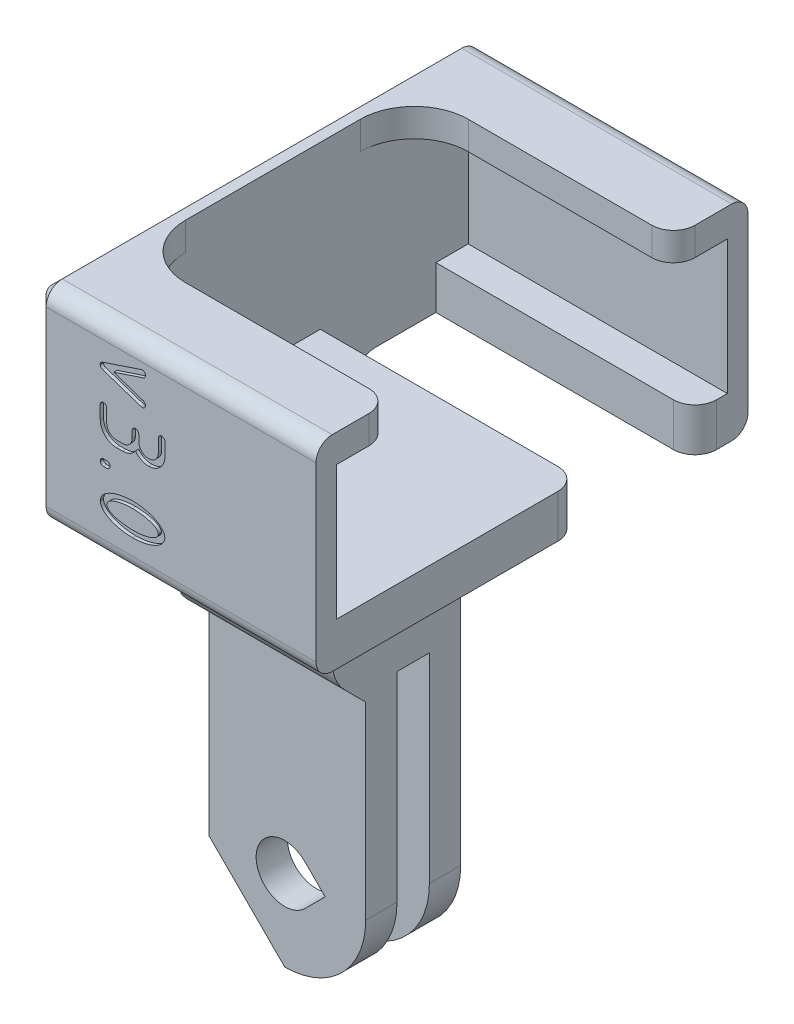
SolidWorks part; units mm, degrees
material "ABS eSun"
ref_plane "Front Plane" through (0, 0, 0) normal (0, 0, 1) x (1, 0, 0)
ref_plane "Top Plane" through (0, 0, 0) normal (0, 1, 0) x (1, 0, 0)
ref_plane "Right Plane" through (0, 0, 0) normal (1, 0, 0) x (0, 0, -1)
ref_axis "AXIS_PIVOT" through (0, 0, 22) along (0, 0, -1)
sketch "Sketch1" plane through (0, 0, 0) normal (0, 0, 1) x (1, 0, 0)
  line L0 (-7.5, 0) -> (-7.5, 32.5)
  line L1 (7.5, 0) -> (7.5, 32.5)
  line L2 (-7.5, 32.5) -> (7.5, 32.5)
  circle A0 centre (0, 0) radius 2.65
  arc A1 (-7.5, 0) -> (7.5, 0) centre (0, 0) ccw
  point P5 (0, -7.5)
  dimension "D1" = 5.3
  dimension "D2" = 15
  dimension "D3" = 40
extrude "boss fingers" add sketch "Sketch1" along normal mid plane 15
sketch "Sketch2" plane through (-7.5, 0, 0) normal (-1, 0, 0) x (0, 0, 1)
  line L0 (-7.5, -7.5) -> (7.5, -7.5) construction
  line L1 (-7.5, -7.5) -> (-4.4, -7.5)
  line L2 (-7.5, -7.5) -> (-7.5, 17.5)
  line L3 (-7.5, 17.5) -> (-4.4, 17.5) construction
  line L4 (-4.4, -7.5) -> (-4.4, 17.5)
  line L5 (7.5, 32.5) -> (7.5, 0) construction
  line L6 (1.5, -7.5) -> (-1.5, -7.5)
  line L7 (1.5, -7.5) -> (1.5, 17.5)
  line L8 (1.5, 17.5) -> (-1.5, 17.5)
  line L9 (-1.5, -7.5) -> (-1.5, 17.5)
  line L10 (4.4, -7.5) -> (7.5, -7.5)
  line L11 (4.4, -7.5) -> (4.4, 17.5)
  line L12 (4.4, 17.5) -> (7.5, 17.5) construction
  line L13 (7.5, -7.5) -> (7.5, 17.5)
  line L14 (-4.4, 17.5) -> (-1.5, 17.5) construction
  line L15 (1.5, 17.5) -> (4.4, 17.5) construction
  line L18 (-4.4, 17.5) -> (-7.5, 20.6)
  line L19 (-7.5, 32.5) -> (-7.5, 0) construction
  line L20 (-7.5, 20.6) -> (-7.5, 17.5)
  line L21 (4.4, 17.5) -> (7.5, 20.6)
  line L22 (7.5, 20.6) -> (7.5, 17.5)
  point P16 (0, 17.5)
  dimension "D1" = 2.9
  dimension "D2" = 25
  dimension "D3" = 3
extrude "cut fingers" cut sketch "Sketch2" against normal through all
sketch "Sketch6" plane through (0, 0, 4.4) normal (0, 0, 1) x (1, 0, 0)
  line L0 (-7.5, 0) -> (0, -7.5)
  line L1 (0, -7.5) -> (-7.5, -7.5)
  line L2 (-7.5, -7.5) -> (-7.5, 0)
  arc A0 (-7.5, 0) -> (7.5, 0) centre (0, 0) ccw construction
extrude "cut overhang" cut sketch "Sketch6" against normal through all
chamfer "chamf_gp_web" distance 1 angle 45 2 edges at (-7.5, 17.5, 0) (7.5, 17.5, 0)
sketch "Sketch7" plane through (0, 0, 4.4) normal (0, 0, 1) x (1, 0, 0)
  line L0 (1.8738, 1.8738) -> (3.7477, 0)
  line L1 (3.7477, 0) -> (1.8738, -1.8738)
  line L2 (0, 0) -> (3.7477, 0) construction
  arc A0 (1.8738, 1.8738) -> (1.8738, -1.8738) centre (0, 0) ccw
  circle A1 centre (0, 0) radius 2.65 construction
extrude "cut_GoPro_tearDrop" cut sketch "Sketch7" against normal through all
chamfer "chamf_gp_base" distance 0.5 angle 45 6 edges at (-7.5, 19.05, -5.95) (-7.5, 8.75, -4.4) (-7.5, 9.25, 1.5) (-7.5, 9.25, -1.5) (-7.5, 19.05, 5.95) (-7.5, 8.75, 4.4)
sketch "Sketch3" plane through (-7.5, 0, 0) normal (-1, 0, 0) x (0, 0, 1)
  line L0 (7.5, 32.5) -> (-7.5, 32.5) construction
  line L1 (-20, 51.5) -> (20, 51.5)
  line L2 (-20, 51.5) -> (-20, 32.5)
  line L3 (-20, 32.5) -> (20, 32.5)
  line L4 (20, 51.5) -> (20, 32.5)
  point P4 (0, 32.5)
  point P7 (0, 32.5)
  dimension "D1" = 40
  dimension "D2" = 19
extrude "boss block" add sketch "Sketch3" against normal blind 26
fillet "Fillet5" radius 2 3 edges at (0, 32.5, -7.5) (0, 32.5, 7.5) (7.5, 32.5, 0)
sketch "Sketch4" plane through (18.5, 0, 0) normal (1, 0, 0) x (0, 0, -1)
  line L0 (-20, 51.5) -> (20, 51.5) construction
  line L1 (-18.1, 36.5) -> (18.1, 36.5)
  line L2 (-18.1, 36.5) -> (-18.1, 48.9)
  line L3 (-18.1, 48.9) -> (-13.1, 48.9)
  line L4 (18.1, 36.5) -> (18.1, 48.9)
  line L5 (-13.1, 51.5) -> (13.1, 51.5)
  line L6 (-13.1, 51.5) -> (-13.1, 48.9)
  line L8 (13.1, 51.5) -> (13.1, 48.9)
  line L9 (-1.5, 17.5) -> (1.5, 17.5) construction
  line L10 (20, 32.5) -> (-20, 32.5) construction
  line L11 (13.1, 48.9) -> (18.1, 48.9)
  point P10 (0, 51.5)
  point P11 (0, 36.5)
  point P14 (0, 17.5)
  dimension "D1" = 36.2
  dimension "D2" = 12.4
  dimension "D3" = 4
  dimension "D4" = 5
extrude "cut camera pocket" cut sketch "Sketch4" against normal offset from surface (24 mm away) 2 up to face at (-7.5, 22.7698, 0)
sketch "Sketch5" plane through (0, 32.5, 0) normal (0, -1, 0) x (1, 0, 0)
  line L0 (-5.5, -18.1) -> (-5.5, 18.1) construction
  line L1 (-5.5, -15.1) -> (18.5, -15.1)
  line L2 (-5.5, -15.1) -> (-5.5, -4.4)
  line L3 (-5.5, -4.4) -> (18.5, -4.4)
  line L4 (18.5, -15.1) -> (18.5, -4.4)
  line L5 (18.5, -20) -> (18.5, 20) construction
  line L6 (-5.5, -18.1) -> (18.5, -18.1) construction
  line L7 (0, -4.4) -> (7.5, -4.4) construction
  dimension "D2" = 3
extrude "cut cable exit" cut sketch "Sketch5" against normal up to surface (4 mm away) and the other way up to vertex (15 mm away) contours L3 L4 L1 L2 up to face at (6.5, 36.5, 0) other way up to point (7.5, 17.5, -4.4)
fillet "fillet outside vert" radius 1.5 4 edges at (5.5, 51.5, 20) (5.5, 32.5, 20) (5.5, 51.5, -20) (5.5, 32.5, -20)
fillet "fillet_cam_top" radius 2 4 edges at (18.5, 50.2, 13.1) (18.5, 50.2, -13.1) (18.5, 34.5, -4.4) (18.5, 34.5, -15.1)
chamfer "chamf_cam_base" distance 1 angle 45 13 edges at (-7.5, 32.5, 14) (-7.5, 32.9393, 19.5607) (-7.5, 42, 20) (-7.5, 51.0607, 19.5607) (-7.5, 51.5, 0) (-7.5, 32.5, -14) (-7.5, 51.0607, -19.5607) (-7.5, 32.9393, -19.5607) (-7.5, 42, -20) (-7.5, 25.9036, 7.5) (-7.5, 31.9142, 8.0858) (-7.5, 25.9036, -7.5) (-7.5, 31.9142, -8.0858)
fillet "fillet_cam_front" radius 5 2 edges at (-5.5, 50.2, 13.1) (-5.5, 50.2, -13.1)
fillet "Fillet6" radius 4 2 edges at (0.5, 20.6, 7.5) (-6, 20.6, -7.5)
sketch "Sketch9" plane through (0, 0, 20) normal (0, 0, 1) x (1, 0, 0)
  line L0 (-1.5, 50) -> (-1.5, 34) construction
  line L1 (18.5, 50) -> (-6.5, 50) construction
  line L2 (-6.5, 34) -> (18.5, 34) construction
  line L3 (-7.5, 34) -> (-7.5, 50) construction
  text T0 "v3.0" font "DS ISO 1" height 6
  dimension "D1" = 6
extrude "version Number" cut sketch "Sketch9" against normal blind 0.3
ref_plane "HORIZON" through (12.71, 0, 0) normal (1, 0, 0) x (0, 0, -1)
